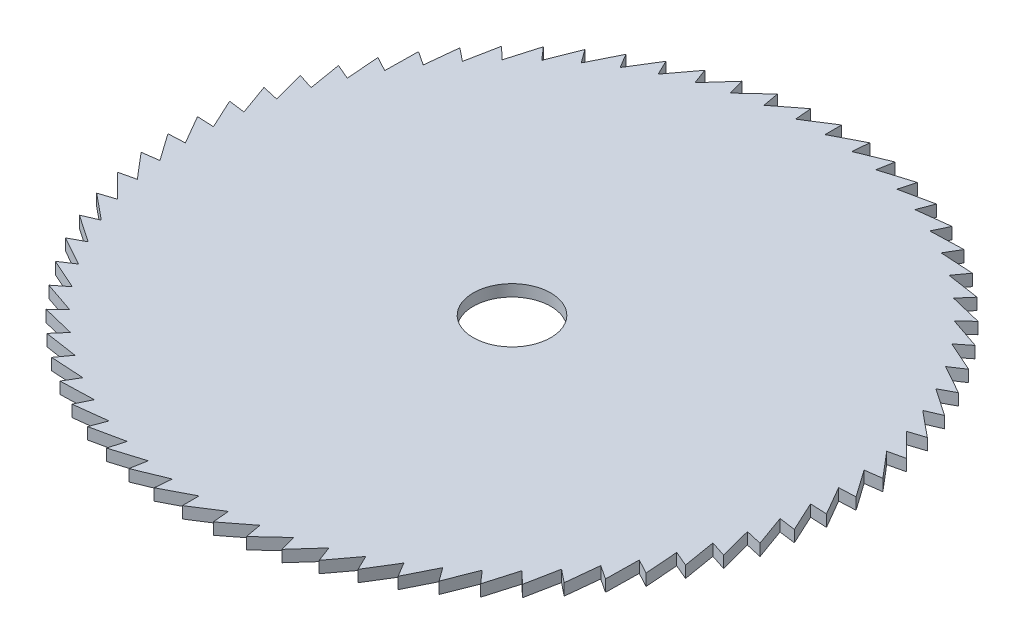
SolidWorks part; units mm, degrees
ref_plane "정면" through (0, 0, 0) normal (0, 0, 1) x (1, 0, 0)
ref_plane "윗면" through (0, 0, 0) normal (0, 1, 0) x (1, 0, 0)
ref_plane "우측면" through (0, 0, 0) normal (1, 0, 0) x (0, 0, -1)
sketch "스케치1" plane through (0, 0, 0) normal (0, 1, 0) x (1, 0, 0)
  circle A0 centre (0, 0) radius 25.5
  circle A1 centre (0, 0) radius 3
  dimension "D1" = 51
  dimension "D2" = 6
extrude "보스-돌출1" add sketch "스케치1" along normal blind 0.9
sketch "스케치3" plane through (0, 0.9, 0) normal (0, 1, 0) x (1, 0, 0)
  line L0 (0, 0) -> (0, 28.1575) construction
  line L1 (0, 25.5) -> (0, 24.2)
  line L2 (0, 25.5) -> (0, 26.1749)
  line L3 (0, 26.1749) -> (3.7978, 26.1749)
  line L4 (3.7978, 26.1749) -> (0, 24.2)
  line L5 (2.3, 25.3961) -> (0, 25.3961) construction
  circle A0 centre (0, 0) radius 25.5 construction
  dimension "D1" = 1.3
  dimension "D2" = 2.3
extrude "컷-돌출2" cut sketch "스케치3" against normal blind 0.9
pattern_circular "원형 패턴1" count 70 over 360 about axis through (0, 0.9, 0) along (0, -1, 0) of "컷-돌출2"
